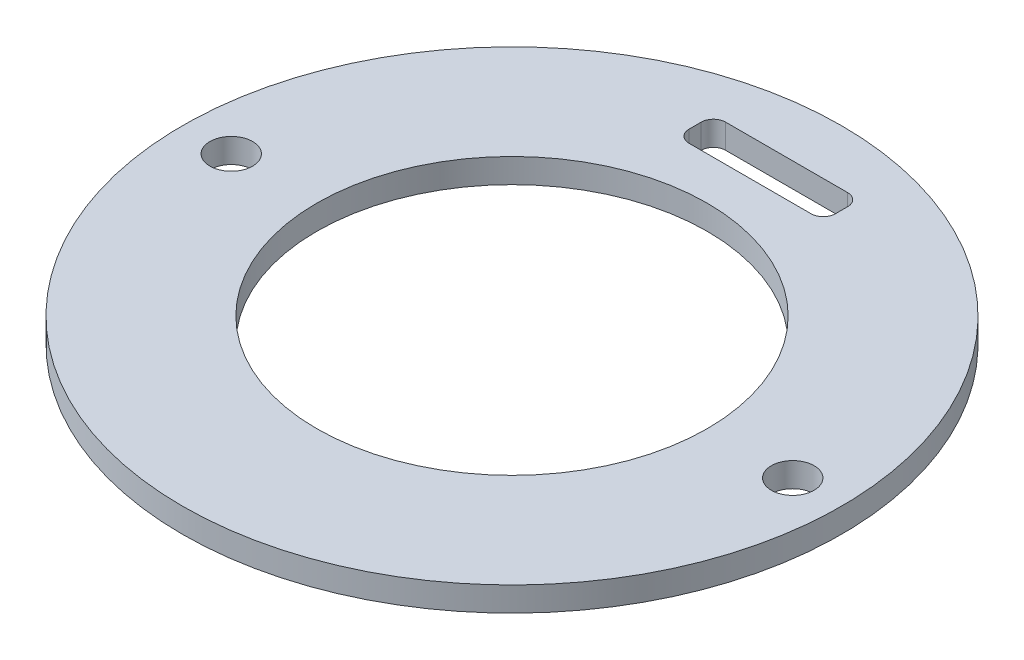
SolidWorks part; units mm, degrees
ref_plane "Front Plane" through (0, 0, 0) normal (0, 0, 1) x (1, 0, 0)
ref_plane "Top Plane" through (0, 0, 0) normal (0, 1, 0) x (1, 0, 0)
ref_plane "Right Plane" through (0, 0, 0) normal (1, 0, 0) x (0, 0, -1)
sketch "Sketch1" plane through (0, 0, 0) normal (0, 1, 0) x (1, 0, 0)
  line L0 (-25, 0) -> (25, 0) construction
  circle A0 centre (0, 0) radius 16
  circle A1 centre (0, 0) radius 27
  circle A2 centre (0, 0) radius 25 construction
  circle A3 centre (-23, 0) radius 1.75
  circle A4 centre (23, 0) radius 1.75
  dimension "D1" = 32
  dimension "D2" = 54
  dimension "D3" = 50
  dimension "D4" = 3.5
  dimension "D6" = 3.5
  dimension "D5" = 2
  dimension "D7" = 2
extrude "Boss-Extrude1" add sketch "Sketch1" along normal blind 2
sketch "Sketch2" plane through (0, 2, 0) normal (0, 1, 0) x (1, 0, 0)
  line L0 (0, 27) -> (0, -27) construction
  line L1 (0, 16) -> (-21.7486, 16) construction
  line L2 (-6, 22.5) -> (6, 22.5)
  line L3 (-6, 22.5) -> (-6, 19.5)
  line L4 (-6, 19.5) -> (6, 19.5)
  line L5 (6, 22.5) -> (6, 19.5)
  line L6 (-6, 22.5) -> (6, 19.5) construction
  line L7 (-6, 19.5) -> (6, 22.5) construction
  circle A0 centre (0, 0) radius 27 construction
  circle A1 centre (0, 0) radius 16 construction
  point P5 (0, 21)
  point P10 (-21.7486, 16)
  dimension "D1" = 12
  dimension "D2" = 3
  dimension "D3" = 5
extrude "Cut-Extrude1" cut sketch "Sketch2" against normal through all
fillet "Fillet1" radius 1 4 edges at (-6, 1, -19.5) (6, 1, -22.5) (6, 1, -19.5) (-6, 1, -22.5)
